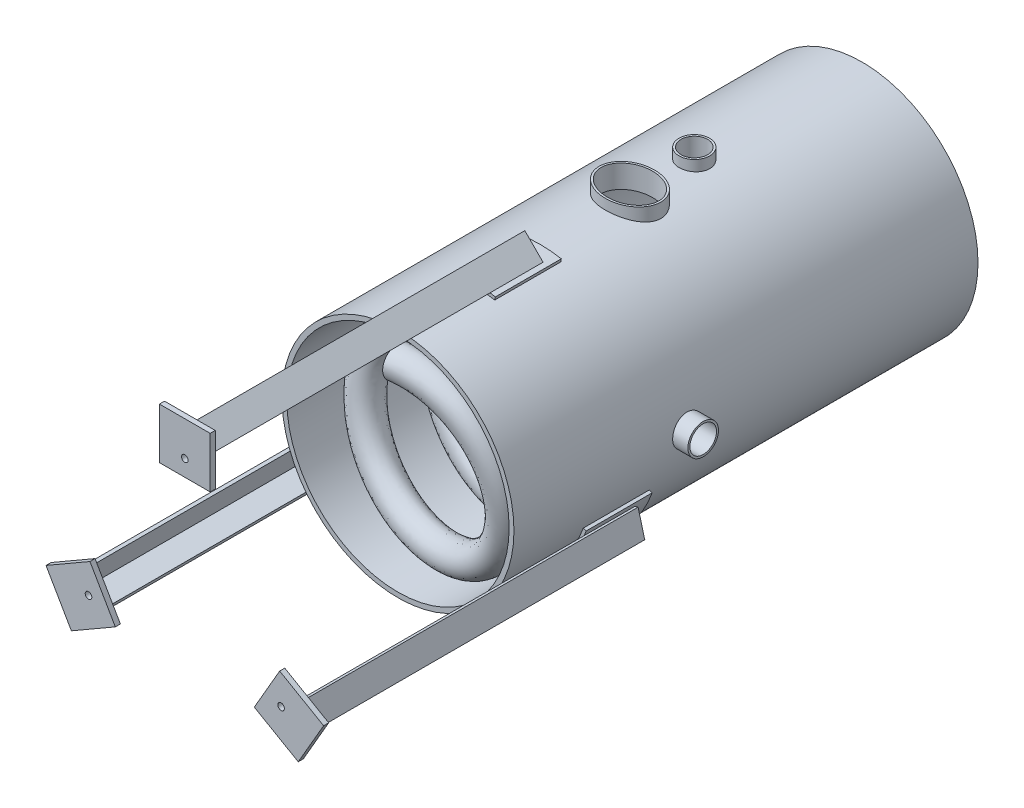
SolidWorks part; units mm, degrees
material "ASTM A36 Acero"
ref_plane "Alzado" through (0, 0, 0) normal (0, 0, 1) x (1, 0, 0)
ref_plane "Planta" through (0, 0, 0) normal (0, 1, 0) x (1, 0, 0)
ref_plane "Vista lateral" through (0, 0, 0) normal (1, 0, 0) x (0, 0, -1)
sketch "Croquis2" plane through (0, 0, 0) normal (0, 0, 1) x (1, 0, 0)
  circle A0 centre (0, 0) radius 228.6
  dimension "D1" = 457.2
extrude "Saliente-Extruir1" add sketch "Croquis2" along normal mid plane 914.4
shell "Vaciado1" thickness 9.525
ref_plane "Plano1" through (0, 0, 457.2) normal (0, 0, 1) x (1, 0, 0)
ref_plane "Plano2" through (0, 0, 207.2) normal (0, 0, 1) x (1, 0, 0)
sketch "Croquis3" plane through (0, 0, 207.2) normal (0, 0, 1) x (1, 0, 0)
  line L0 (0, 0) -> (0, 228.6)
  line L1 (0, 0) -> (197.9734, -114.3)
  line L2 (0, 0) -> (-197.9734, -114.3)
  line L3 (-41.5, 228.6) -> (41.5, 228.6) construction
  line L10 (0, 0) -> (197.9734, -114.3)
  line L17 (215.2059, -77.0998) -> (220.8544, -79.1234)
  line L18 (0, 0) -> (-197.9734, -114.3)
  line L25 (-40.8326, 224.9237) -> (-41.9043, 230.8272)
  line L26 (40.8326, 224.9237) -> (41.9043, 230.8272)
  line L27 (174.3733, -147.8239) -> (178.95, -151.7038)
  line L28 (-174.3733, -147.8239) -> (-178.95, -151.7038)
  line L29 (-215.2059, -77.0998) -> (-220.8544, -79.1234)
  circle A0 centre (0, 0) radius 228.6 construction
  arc A1 (-167.1875, 155.9048) -> (-40.8326, 224.9237) centre (0, 0) ccw
  arc A2 (-197.9734, -114.3) -> (-40.8326, 224.9237) centre (0, 0) ccw construction
  arc A3 (-167.1875, 155.9048) -> (-40.8326, 224.9237) centre (0, 0) ccw construction
  arc A4 (41.9043, 230.8272) -> (-41.9043, 230.8272) centre (0, 0) ccw
  circle A5 centre (0, 0) radius 234.6 construction
  circle A6 centre (0, 0) radius 228.6 construction
  arc A7 (218.6113, 66.8362) -> (215.2059, -77.0998) centre (0, 0) ccw
  arc A8 (178.95, -151.7038) -> (220.8544, -79.1234) centre (0, 0) ccw
  arc A9 (-51.4238, -222.741) -> (-174.3733, -147.8239) centre (0, 0) ccw
  arc A10 (-220.8544, -79.1234) -> (-178.95, -151.7038) centre (0, 0) ccw
  point P8 (0, 0)
  point P13 (0, 228.6)
  point P30 (0, 0)
  point P32 (0, 0)
  dimension "D2" = 6
  dimension "D3" = 3
  dimension "D1" = 3
  dimension "D6" = 3
extrude "Saliente-Extruir5" add sketch "Croquis3" along normal blind 100 and the other way blind 30 contours L26 A4 L25 A1 | L29 A10 L28 A1 | L27 A8 L17 A1
sketch "Croquis8" plane through (0, 0, 207.2) normal (0, 0, 1) x (1, 0, 0)
  line L0 (0, 234.6) -> (0, 201.07)
  line L1 (0, 234.6) -> (0, 263.86) construction
  line L2 (0, 263.86) -> (-31.3955, 232.4645)
  line L3 (0, 263.86) -> (31.3955, 232.4645)
  line L4 (0, 272.9025) -> (35.9168, 236.9857)
  line L5 (0, 272.9025) -> (-35.9168, 236.9857)
  line L6 (-35.9168, 236.9857) -> (-31.3955, 232.4645)
  line L7 (35.9168, 236.9857) -> (31.3955, 232.4645)
  line L8 (187.2772, -149.5977) -> (185.6224, -143.4216)
  line L9 (228.5095, -131.93) -> (185.6224, -143.4216)
  line L10 (228.5095, -131.93) -> (217.0179, -89.0429)
  line L11 (223.194, -87.388) -> (217.0179, -89.0429)
  line L12 (236.3405, -136.4512) -> (223.194, -87.388)
  line L13 (236.3405, -136.4512) -> (187.2772, -149.5977)
  line L14 (-223.194, -87.388) -> (-217.0179, -89.0429)
  line L15 (-228.5095, -131.93) -> (-217.0179, -89.0429)
  line L16 (-228.5095, -131.93) -> (-185.6224, -143.4216)
  line L17 (-187.2772, -149.5977) -> (-185.6224, -143.4216)
  line L18 (-236.3405, -136.4512) -> (-187.2772, -149.5977)
  line L19 (-236.3405, -136.4512) -> (-223.194, -87.388)
  arc A0 (41.9043, 230.8272) -> (-41.9043, 230.8272) centre (0, 0) ccw construction
  arc A1 (41.9043, 230.8272) -> (-41.9043, 230.8272) centre (0, 0) ccw construction
  point P27 (0, 0)
  dimension "D1" = 45
  dimension "D2" = 45
  dimension "D3" = 44.4
  dimension "D4" = 44.4
  dimension "D5" = 6.394
  dimension "D6" = 3
extrude "Saliente-Extruir6" add sketch "Croquis8" along normal blind 670 contours L19 L18 L17 L16 L15 L14 | L13 L12 L11 L10 L9 L8 | L2 L6 L5 L4 L7 L3
sketch "Croquis10" plane through (0, 0, 877.2) normal (0, 0, 1) x (1, 0, 0)
  line L0 (0, 272.9025) -> (0, 201.0625)
  line L1 (273.5341, -100.19) -> (186.9316, -50.19)
  line L2 (-50, 286.9825) -> (50, 286.9825)
  line L3 (-50, 286.9825) -> (-50, 186.9825)
  line L4 (-50, 186.9825) -> (50, 186.9825)
  line L5 (50, 286.9825) -> (50, 186.9825)
  line L6 (-50, 286.9825) -> (50, 186.9825) construction
  line L7 (-50, 186.9825) -> (50, 286.9825) construction
  line L8 (273.5341, -100.19) -> (223.5341, -186.7925)
  line L9 (223.5341, -186.7925) -> (136.9316, -136.7925)
  line L10 (186.9316, -50.19) -> (136.9316, -136.7925)
  line L11 (-223.5341, -186.7925) -> (-136.9316, -136.7925)
  line L12 (-223.5341, -186.7925) -> (-273.5341, -100.19)
  line L13 (-273.5341, -100.19) -> (-186.9316, -50.19)
  line L14 (-136.9316, -136.7925) -> (-186.9316, -50.19)
  point P4 (0, 236.9825)
  point P19 (0, 0)
  dimension "D1" = 100
  dimension "D2" = 100
  dimension "D3" = 3
extrude "Saliente-Extruir7" add sketch "Croquis10" against normal blind 10
sketch "Croquis11" plane through (0, 0, 457.2) normal (0, 0, 1) x (1, 0, 0)
  line L0 (0, 0) -> (197.9734, 114.3)
  line L1 (0, 0) -> (0, 228.6)
  line L2 (0, 0) -> (197.9734, -114.3)
  line L3 (0, 0) -> (0, -228.6)
  line L4 (0, 0) -> (-197.9734, -114.3)
  line L5 (0, 0) -> (-197.9734, 114.3)
  point P12 (0, 0)
  dimension "D1" = 228.6
  dimension "D2" = 6
ref_plane "Plano3" through (197.9734, 114.3, 0) normal (0.866, 0.5, 0) x (0, 0, -1)
ref_plane "Plano4" through (223.9542, 129.3, 0) normal (0.866, 0.5, 0) x (0, 0, -1)
sketch "Croquis13" plane through (223.9542, 129.3, 0) normal (0.866, 0.5, 0) x (0, 0, -1)
  line L0 (-457.2, 0) -> (-257.2, 0) construction
  line L1 (-867.2, 0) -> (-207.2, 0) construction
  line L2 (-257.2, -50) -> (-257.2, 50) construction
  circle A0 centre (-257.2, 50) radius 16.7
  circle A1 centre (-257.2, -50) radius 16.7
  point P9 (-257.2, 0)
  point P11 (0, 0)
  dimension "D3" = 33.4
  dimension "D1" = 200
  dimension "D2" = 100
ref_plane "Plano5" through (225.1271, -39.696, 0) normal (0.9848, -0.1736, 0) x (0, 0, -1)
ref_plane "Plano6" through (244.8232, -43.1689, 0) normal (0.9848, -0.1736, 0) x (0, 0, -1)
sketch "Croquis16" plane through (244.8232, -43.1689, 0) normal (0.9848, -0.1736, 0) x (0, 0, -1)
  circle A0 centre (-134.0081, 0) radius 10.65
  point P2 (0, 0)
  dimension "D1" = 21.3
ref_plane "Plano7" through (0, 228.6, 0) normal (0, 1, 0) x (1, 0, 0)
ref_plane "Plano8" through (0, 248.6, 0) normal (0, 1, 0) x (1, 0, 0)
sketch "Croquis19" plane through (0, 248.6, 0) normal (0, 1, 0) x (1, 0, 0)
  line L0 (-60.91, 0) -> (60.91, 0) construction
  line L1 (0, 0) -> (0, 48.41) construction
  ellipse E0 centre (0, 0) end of major axis (-60.91, 0) minor radius 48.41
  point P4 (0, 0)
  dimension "D1" = 121.82
  dimension "D2" = 48.41
extrude "Saliente-Extruir10" add sketch "Croquis19" against normal blind 45
sketch "Croquis20" plane through (0, 248.6, 0) normal (0, 1, 0) x (1, 0, 0)
  spline S0 degree 3 poles (57, -0.8433) (57, 1.6865) (56.877, 3.3513) (56.3988, 6.6397) (56.0435, 8.2633) (55.3398, 10.6686) (55.0761, 11.4669) (54.4939, 13.0464) (54.1776, 13.8223) (53.1567, 16.1106) (52.3805, 17.5837) (51.0834, 19.7203) (50.6289, 20.4202) (49.6763, 21.7964) (49.177, 22.4743) (47.6253, 24.4597) (46.5234, 25.715) (44.1981, 28.1019) (42.9746, 29.2335) (41.0538, 30.8441) (40.3992, 31.3664) (39.0621, 32.3827) (38.382, 32.8746) (34.9434, 35.2454) (32.0552, 36.8731) (27.5444, 38.9645) (26.0107, 39.6028) (22.8851, 40.765) (21.2873, 41.2903) (16.4718, 42.6782) (13.2205, 43.3607) (8.2865, 44.0448) (6.6323, 44.2159) (4.1365, 44.387) (3.3022, 44.4298) (1.6287, 44.4866) (0.7903, 44.5005) (-3.3843, 44.4979) (-6.6918, 44.2676) (-13.2432, 43.3558) (-16.487, 42.6746) (-20.4988, 41.5174) (-21.3004, 41.2701) (-22.892, 40.7458) (-23.6806, 40.4694) (-26.0246, 39.5973) (-27.5583, 38.9586) (-32.0698, 36.8654) (-34.9592, 35.2361) (-38.4001, 32.8618) (-39.0812, 32.3686) (-40.4168, 31.3526) (-41.0704, 30.8306) (-42.9875, 29.2219) (-44.2076, 28.0926) (-46.5248, 25.7132) (-47.6219, 24.4632) (-49.6808, 21.8305) (-50.6462, 20.4401) (-52.381, 17.5832) (-53.1563, 16.1107) (-54.5122, 13.073) (-55.093, 11.5077) (-55.8042, 9.0835) (-56.0129, 8.2672) (-56.3699, 6.6342) (-56.5188, 5.815) (-56.8772, 3.3494) (-56.9985, 1.6951) (-57.0007, -0.8026) (-56.9714, -1.6379) (-56.8511, -3.314) (-56.7598, -4.1552) (-56.3986, -6.6444) (-56.0411, -8.2724) (-55.1054, -11.469) (-54.5272, -13.0376) (-53.1545, -16.1165) (-52.3724, -17.5986) (-50.6396, -20.4499) (-49.6881, -21.8207) (-48.141, -23.7996) (-47.6045, -24.4473) (-46.4958, -25.7133) (-45.9267, -26.3282) (-43.0115, -29.3175) (-40.4595, -31.44) (-37.0338, -33.8047) (-36.3367, -34.2631) (-34.9191, -35.151) (-34.197, -35.5816) (-32.0084, -36.8238) (-30.5241, -37.584) (-26.0019, -39.6777) (-22.895, -40.8258) (-18.1082, -42.2071) (-16.4914, -42.6104) (-14.0345, -43.13) (-13.2098, -43.2889) (-11.5621, -43.5764) (-10.7377, -43.7051) (-6.6122, -44.2761) (-3.3019, -44.5008) (1.6783, -44.4996) (3.3408, -44.4424) (6.6709, -44.2123) (8.344, -44.0384) (13.3026, -43.3461) (16.5428, -42.6595) (22.8893, -40.8268) (25.9958, -39.6812) (29.7848, -37.9261) (30.5389, -37.5583) (32.0325, -36.7906) (32.769, -36.3925) (34.9472, -35.1548) (36.3575, -34.2717) (39.0907, -32.3846) (40.4136, -31.3806) (42.3272, -29.7765) (42.9532, -29.2254) (44.1804, -28.0888) (44.7824, -27.5025) (47.7173, -24.4882) (49.7763, -21.8711) (51.9408, -18.3086) (52.353, -17.5814) (53.1337, -16.0958) (53.5033, -15.3347) (54.528, -13.0349) (55.1034, -11.4736) (56.0354, -8.2938) (56.3921, -6.6754) (56.754, -4.2026) (56.8457, -3.3707) (56.9688, -1.6914) (57, -0.8433) (57, 1.6865) (56.877, 3.3513) knots -0.007812 -0.007812 0 0 0.015625 0.015625 0.03125 0.03125 0.039063 0.039063 0.046875 0.046875 0.0625 0.0625 0.070313 0.070313 0.078125 0.078125 0.09375 0.09375 0.109375 0.109375 0.117188 0.117188 0.125 0.125 0.15625 0.15625 0.171875 0.171875 0.1875 0.1875 0.21875 0.21875 0.234375 0.234375 0.242188 0.242188 0.25 0.25 0.28125 0.28125 0.3125 0.3125 0.320313 0.320313 0.328125 0.328125 0.34375 0.34375 0.375 0.375 0.382813 0.382813 0.390625 0.390625 0.40625 0.40625 0.421875 0.421875 0.4375 0.4375 0.453125 0.453125 0.46875 0.46875 0.476563 0.476563 0.484375 0.484375 0.5 0.5 0.507813 0.507813 0.515625 0.515625 0.53125 0.53125 0.546875 0.546875 0.5625 0.5625 0.578125 0.578125 0.585938 0.585938 0.59375 0.59375 0.625 0.625 0.632813 0.632813 0.640625 0.640625 0.65625 0.65625 0.6875 0.6875 0.703125 0.703125 0.710938 0.710938 0.71875 0.71875 0.75 0.75 0.765625 0.765625 0.78125 0.78125 0.8125 0.8125 0.84375 0.84375 0.851563 0.851563 0.859375 0.859375 0.875 0.875 0.890625 0.890625 0.898438 0.898438 0.90625 0.90625 0.9375 0.9375 0.945313 0.945313 0.953125 0.953125 0.96875 0.96875 0.984375 0.984375 0.992188 0.992188 1 1 1.015625 1.015625 1.03125 only from (57, 0) to (57, 0)
  spline S1 degree 3 poles (57, -0.8433) (57, 1.6865) (56.877, 3.3513) (56.3988, 6.6397) (56.0435, 8.2633) (55.3398, 10.6686) (55.0761, 11.4669) (54.4939, 13.0464) (54.1776, 13.8223) (53.1567, 16.1106) (52.3805, 17.5837) (51.0834, 19.7203) (50.6289, 20.4202) (49.6763, 21.7964) (49.177, 22.4743) (47.6253, 24.4597) (46.5234, 25.715) (44.1981, 28.1019) (42.9746, 29.2335) (41.0538, 30.8441) (40.3992, 31.3664) (39.0621, 32.3827) (38.382, 32.8746) (34.9434, 35.2454) (32.0552, 36.8731) (27.5444, 38.9645) (26.0107, 39.6028) (22.8851, 40.765) (21.2873, 41.2903) (16.4718, 42.6782) (13.2205, 43.3607) (8.2865, 44.0448) (6.6323, 44.2159) (4.1365, 44.387) (3.3022, 44.4298) (1.6287, 44.4866) (0.7903, 44.5005) (-3.3843, 44.4979) (-6.6918, 44.2676) (-13.2432, 43.3558) (-16.487, 42.6746) (-20.4988, 41.5174) (-21.3004, 41.2701) (-22.892, 40.7458) (-23.6806, 40.4694) (-26.0246, 39.5973) (-27.5583, 38.9586) (-32.0698, 36.8654) (-34.9592, 35.2361) (-38.4001, 32.8618) (-39.0812, 32.3686) (-40.4168, 31.3526) (-41.0704, 30.8306) (-42.9875, 29.2219) (-44.2076, 28.0926) (-46.5248, 25.7132) (-47.6219, 24.4632) (-49.6808, 21.8305) (-50.6462, 20.4401) (-52.381, 17.5832) (-53.1563, 16.1107) (-54.5122, 13.073) (-55.093, 11.5077) (-55.8042, 9.0835) (-56.0129, 8.2672) (-56.3699, 6.6342) (-56.5188, 5.815) (-56.8772, 3.3494) (-56.9985, 1.6951) (-57.0007, -0.8026) (-56.9714, -1.6379) (-56.8511, -3.314) (-56.7598, -4.1552) (-56.3986, -6.6444) (-56.0411, -8.2724) (-55.1054, -11.469) (-54.5272, -13.0376) (-53.1545, -16.1165) (-52.3724, -17.5986) (-50.6396, -20.4499) (-49.6881, -21.8207) (-48.141, -23.7996) (-47.6045, -24.4473) (-46.4958, -25.7133) (-45.9267, -26.3282) (-43.0115, -29.3175) (-40.4595, -31.44) (-37.0338, -33.8047) (-36.3367, -34.2631) (-34.9191, -35.151) (-34.197, -35.5816) (-32.0084, -36.8238) (-30.5241, -37.584) (-26.0019, -39.6777) (-22.895, -40.8258) (-18.1082, -42.2071) (-16.4914, -42.6104) (-14.0345, -43.13) (-13.2098, -43.2889) (-11.5621, -43.5764) (-10.7377, -43.7051) (-6.6122, -44.2761) (-3.3019, -44.5008) (1.6783, -44.4996) (3.3408, -44.4424) (6.6709, -44.2123) (8.344, -44.0384) (13.3026, -43.3461) (16.5428, -42.6595) (22.8893, -40.8268) (25.9958, -39.6812) (29.7848, -37.9261) (30.5389, -37.5583) (32.0325, -36.7906) (32.769, -36.3925) (34.9472, -35.1548) (36.3575, -34.2717) (39.0907, -32.3846) (40.4136, -31.3806) (42.3272, -29.7765) (42.9532, -29.2254) (44.1804, -28.0888) (44.7824, -27.5025) (47.7173, -24.4882) (49.7763, -21.8711) (51.9408, -18.3086) (52.353, -17.5814) (53.1337, -16.0958) (53.5033, -15.3347) (54.528, -13.0349) (55.1034, -11.4736) (56.0354, -8.2938) (56.3921, -6.6754) (56.754, -4.2026) (56.8457, -3.3707) (56.9688, -1.6914) (57, -0.8433) (57, 1.6865) (56.877, 3.3513) knots -0.007812 -0.007812 0 0 0.015625 0.015625 0.03125 0.03125 0.039063 0.039063 0.046875 0.046875 0.0625 0.0625 0.070313 0.070313 0.078125 0.078125 0.09375 0.09375 0.109375 0.109375 0.117188 0.117188 0.125 0.125 0.15625 0.15625 0.171875 0.171875 0.1875 0.1875 0.21875 0.21875 0.234375 0.234375 0.242188 0.242188 0.25 0.25 0.28125 0.28125 0.3125 0.3125 0.320313 0.320313 0.328125 0.328125 0.34375 0.34375 0.375 0.375 0.382813 0.382813 0.390625 0.390625 0.40625 0.40625 0.421875 0.421875 0.4375 0.4375 0.453125 0.453125 0.46875 0.46875 0.476563 0.476563 0.484375 0.484375 0.5 0.5 0.507813 0.507813 0.515625 0.515625 0.53125 0.53125 0.546875 0.546875 0.5625 0.5625 0.578125 0.578125 0.585938 0.585938 0.59375 0.59375 0.625 0.625 0.632813 0.632813 0.640625 0.640625 0.65625 0.65625 0.6875 0.6875 0.703125 0.703125 0.710938 0.710938 0.71875 0.71875 0.75 0.75 0.765625 0.765625 0.78125 0.78125 0.8125 0.8125 0.84375 0.84375 0.851563 0.851563 0.859375 0.859375 0.875 0.875 0.890625 0.890625 0.898438 0.898438 0.90625 0.90625 0.9375 0.9375 0.945313 0.945313 0.953125 0.953125 0.96875 0.96875 0.984375 0.984375 0.992188 0.992188 1 1 1.015625 1.015625 1.03125 only from (57, 0) to (57, 0)
  dimension "D1" = 3.91
extrude "Cortar-Extruir3" cut sketch "Croquis20" against normal up to next
sketch "Croquis21" plane through (0, 248.6, 0) normal (0, 1, 0) x (1, 0, 0)
  line L0 (0, -457.2) -> (0, 0) construction
  line L1 (-228.6, -457.2) -> (228.6, -457.2) construction
  line L2 (0, -457.2) -> (0, 126.8)
  circle A0 centre (0, 126.8) radius 30.15
  dimension "D1" = 60.3
extrude "Saliente-Extruir11" add sketch "Croquis21" against normal blind 45
sketch "Croquis22" plane through (0, 248.6, 0) normal (0, 1, 0) x (1, 0, 0)
  circle A0 centre (0, 126.8) radius 26.24
  dimension "D1" = 52.48
extrude "Cortar-Extruir4" cut sketch "Croquis22" against normal up to next
ref_plane "Plano9" through (0, -228.6, 0) normal (0, -1, 0) x (-1, 0, 0)
ref_plane "Plano10" through (0, -258.6, 0) normal (0, -1, 0) x (-1, 0, 0)
sketch "Croquis23" plane through (0, -258.6, 0) normal (0, -1, 0) x (-1, 0, 0)
  line L0 (0, 457.2) -> (0, 314.325) construction
  line L1 (228.6, 457.2) -> (-228.6, 457.2) construction
  line L2 (0, 314.325) -> (0, 9.525) construction
  circle A0 centre (0, 314.325) radius 16.7
  circle A1 centre (0, 9.525) radius 16.7
  dimension "D2" = 33.4
  dimension "D1" = 142.875
  dimension "D3" = 304.8
extrude "Saliente-Extruir12" add sketch "Croquis23" against normal blind 50
sketch "Croquis25" plane through (0, -258.6, 0) normal (0, -1, 0) x (-1, 0, 0)
  circle A0 centre (0, 314.325) radius 13.32
  circle A1 centre (0, 9.525) radius 13.32
  dimension "D1" = 26.64
extrude "Cortar-Extruir5" cut sketch "Croquis25" against normal up to next
ref_plane "Plano11" through (228.6, 0, 0) normal (1, 0, 0) x (0, 0, -1)
ref_plane "Plano12" through (258.6, 0, 0) normal (1, 0, 0) x (0, 0, -1)
sketch "Croquis27" plane through (258.6, 0, 0) normal (1, 0, 0) x (0, 0, -1)
  line L0 (-457.2, 0) -> (-114.3, 0)
  line L1 (-457.2, 228.6) -> (-457.2, -228.6) construction
  circle A0 centre (-114.3, 0) radius 30.15
  dimension "D2" = 60.3
  dimension "D1" = 342.9
extrude "Saliente-Extruir13" add sketch "Croquis27" against normal blind 50
ref_plane "Plano13" through (0, 0, 457.2) normal (0, 0, 1) x (1, 0, 0)
sketch "Croquis28" plane through (0, 0, 457.2) normal (0, 0, 1) x (1, 0, 0)
  circle A0 centre (0, 0) radius 175
  dimension "D1" = 350
ref_plane "Plano14" through (0, 0, 114.3) normal (0, 0, 1) x (1, 0, 0)
sketch "Croquis29" plane through (0, 0, 114.3) normal (0, 0, 1) x (1, 0, 0)
  circle A0 centre (0, 0) radius 150
curve "Hélice/Espiral1" pitch 150 height 330 turns 2.2
sketch "Croquis30" plane through (0, 0, 0) normal (1, 0, 0) x (0, 0, -1)
  circle A0 centre (-157.2002, 175) radius 30.15
  spline S0 degree 3 poles (-457.2, 175) (-456.3477, 175) (-454.6417, 174.3296) (-452.0838, 171.3241) (-449.5256, 166.3534) (-446.9674, 159.4744) (-444.4093, 150.766) (-441.8512, 140.3282) (-439.293, 128.2806) (-436.7349, 114.7615) (-434.1767, 99.9259) (-431.6186, 83.944) (-429.0605, 66.9992) (-426.5023, 49.2859) (-423.9442, 31.0072) (-421.386, 12.3727) (-418.8279, -6.4036) (-416.2698, -25.1065) (-413.7116, -43.5214) (-411.1535, -61.437) (-408.5953, -78.6479) (-406.0372, -94.9566) (-403.4791, -110.176) (-400.9209, -124.1316) (-398.3628, -136.6632) (-395.8047, -147.6272) (-393.2465, -156.8976) (-390.6884, -164.3683) (-388.1302, -169.9534) (-385.5721, -173.589) (-383.014, -175.2333) (-380.4558, -174.8675) (-377.8977, -172.4957) (-375.3395, -168.1452) (-372.7814, -161.8658) (-370.2233, -153.7296) (-367.6651, -143.83) (-365.107, -132.2805) (-362.5488, -119.2135) (-359.9907, -104.779) (-357.4326, -89.1426) (-354.8744, -72.4836) (-352.3163, -54.9931) (-349.7581, -36.8718) (-347.2, -18.3275) (-344.6419, 0.427) (-342.0837, 19.1766) (-339.5256, 37.7063) (-336.9674, 55.8034) (-334.4093, 73.2603) (-331.8512, 89.8769) (-329.293, 105.4625) (-326.7349, 119.8383) (-324.1767, 132.8394) (-321.6186, 144.3167) (-319.0605, 154.1385) (-316.5023, 162.1921) (-313.9442, 168.3852) (-311.386, 172.6467) (-308.8279, 174.9277) (-306.2698, 175.2021) (-303.7116, 173.4667) (-301.1535, 169.7415) (-298.5953, 164.0691) (-296.0372, 156.5146) (-293.4791, 147.1647) (-290.9209, 136.1266) (-288.3628, 123.527) (-285.8047, 109.5104) (-283.2465, 94.2376) (-280.6884, 77.8837) (-278.1302, 60.6364) (-275.5721, 42.6936) (-273.014, 24.261) (-270.4558, 5.5501) (-267.8977, -13.2245) (-265.3395, -31.8473) (-262.7814, -50.1049) (-260.2233, -67.7876) (-257.6651, -84.6928) (-255.107, -100.6264) (-252.5488, -115.4058) (-249.9907, -128.8612) (-247.4326, -140.8385) (-244.8744, -151.2002) (-242.3163, -159.8274) (-239.7581, -166.6213) (-237.2, -171.5037) (-234.6419, -174.4188) (-232.0837, -175.3331) (-229.5256, -174.2362) (-226.9674, -171.1405) (-224.4093, -166.0816) (-221.8512, -159.1176) (-219.293, -150.3283) (-216.7349, -139.8145) (-214.1767, -127.6969) (-211.6186, -114.1144) (-209.0605, -99.223) (-206.5023, -83.1933) (-203.9442, -66.2093) (-201.386, -48.4657) (-198.8279, -30.1663) (-196.2698, -11.5207) (-193.7116, 7.257) (-191.1535, 25.9514) (-188.5953, 44.3481) (-186.0372, 62.2361) (-183.4791, 79.4102) (-180.9209, 95.6734) (-178.3628, 110.8391) (-175.8047, 124.7333) (-173.2465, 137.1966) (-170.6884, 148.0862) (-168.1302, 157.277) (-165.5721, 164.6636) (-163.014, 170.1614) (-160.4558, 173.7072) (-157.8977, 175.2604) (-155.3395, 174.8031) (-152.7814, 172.3406) (-150.2233, 167.9011) (-147.6651, 161.5356) (-145.107, 153.3171) (-142.5488, 143.3399) (-139.9907, 131.7184) (-137.4326, 118.5858) (-134.8744, 104.0931) (-132.3162, 88.4058) (-129.7583, 71.7064) (-128.0523, 60.02) (-127.2, 54.078) knots 0 0 0 0 0.007752 0.015504 0.023256 0.031008 0.03876 0.046512 0.054264 0.062016 0.069767 0.077519 0.085271 0.093023 0.100775 0.108527 0.116279 0.124031 0.131783 0.139535 0.147287 0.155039 0.162791 0.170543 0.178295 0.186047 0.193798 0.20155 0.209302 0.217054 0.224806 0.232558 0.24031 0.248062 0.255814 0.263566 0.271318 0.27907 0.286822 0.294574 0.302326 0.310078 0.317829 0.325581 0.333333 0.341085 0.348837 0.356589 0.364341 0.372093 0.379845 0.387597 0.395349 0.403101 0.410853 0.418605 0.426357 0.434109 0.44186 0.449612 0.457364 0.465116 0.472868 0.48062 0.488372 0.496124 0.503876 0.511628 0.51938 0.527132 0.534884 0.542636 0.550388 0.55814 0.565891 0.573643 0.581395 0.589147 0.596899 0.604651 0.612403 0.620155 0.627907 0.635659 0.643411 0.651163 0.658915 0.666667 0.674419 0.682171 0.689922 0.697674 0.705426 0.713178 0.72093 0.728682 0.736434 0.744186 0.751938 0.75969 0.767442 0.775194 0.782946 0.790698 0.79845 0.806202 0.813953 0.821705 0.829457 0.837209 0.844961 0.852713 0.860465 0.868217 0.875969 0.883721 0.891473 0.899225 0.906977 0.914729 0.922481 0.930233 0.937984 0.945736 0.953488 0.96124 0.968992 0.976744 0.984496 0.992248 1 1 1 1 construction
  dimension "D1" = 60.3
sweep "Barrer1" add profiles "Croquis30" path "Hélice/Espiral1"
sketch "Croquis33" plane through (258.6, 0, 0) normal (1, 0, 0) x (0, 0, -1)
  circle A0 centre (-114.3, 0) radius 26.24
  dimension "D1" = 52.48
extrude "Cortar-Extruir6" cut sketch "Croquis33" against normal up to next (50 mm away)
sketch "Croquis35" plane through (0, 0, 877.2) normal (0, 0, 1) x (1, 0, 0)
  line L0 (-161.9316, -93.4912) -> (-189.7245, -109.5375) construction
  line L1 (-136.9316, -136.7925) -> (-186.9316, -50.19) construction
  circle A0 centre (0, 0) radius 219.075 construction
  circle A1 centre (-189.7245, -109.5375) radius 6.5
  circle A2 centre (0, 219.075) radius 6.5
  circle A3 centre (189.7245, -109.5375) radius 6.5
  point P14 (0, 0)
  dimension "D1" = 13
  dimension "D2" = 3
extrude "Cortar-Extruir7" cut sketch "Croquis35" against normal up to next (10 mm away)
